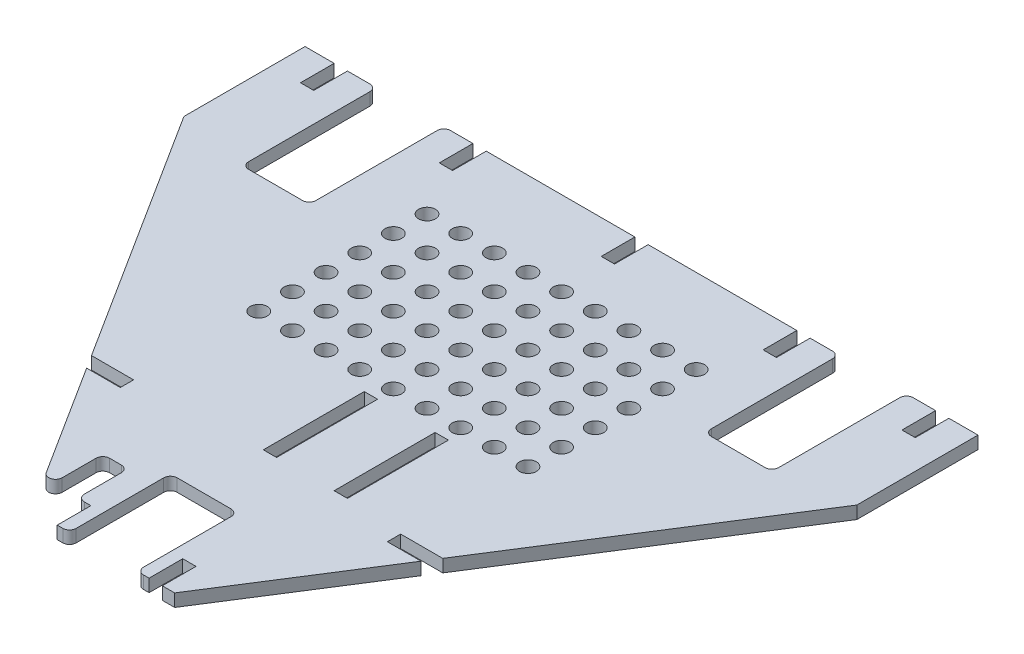
SolidWorks part; units mm, degrees
material "Corrugated Paper"
ref_plane "Front Plane" through (0, 0, 0) normal (0, 0, 1) x (1, 0, 0)
ref_plane "Top Plane" through (0, 0, 0) normal (0, 1, 0) x (1, 0, 0)
ref_plane "Right Plane" through (0, 0, 0) normal (1, 0, 0) x (0, 0, -1)
sketch "Sketch1" plane through (0, 0, 0) normal (0, 1, 0) x (1, 0, 0)
  line L0 (0, 0) -> (0, -142.875) construction
  line L1 (12.7, -63.5) -> (-12.7, -63.5)
  line L2 (-12.7, -63.5) -> (-12.7, -101.6)
  line L3 (-12.7, -101.6) -> (-17.3355, -101.6)
  line L4 (-26.9875, -101.6) -> (-127, 55.88)
  line L5 (-127, 55.88) -> (-127, 101.6)
  line L6 (-127, 101.6) -> (-116.0145, 101.6)
  line L7 (-100.0125, 101.6) -> (-100.0125, 50.8)
  line L9 (-100.0125, 50.8) -> (-74.6125, 50.8)
  line L10 (-74.6125, 50.8) -> (-74.6125, 101.6)
  line L11 (-74.6125, 101.6) -> (-63.627, 101.6)
  line L13 (74.6125, 50.8) -> (74.6125, 101.6)
  line L14 (100.0125, 50.8) -> (74.6125, 50.8)
  line L15 (100.0125, 101.6) -> (100.0125, 50.8)
  line L16 (127, 101.6) -> (116.0145, 101.6)
  line L17 (127, 55.88) -> (127, 101.6)
  line L18 (26.9875, -101.6) -> (127, 55.88)
  line L19 (12.7, -101.6) -> (17.3355, -101.6)
  line L20 (12.7, -63.5) -> (12.7, -101.6)
  line L21 (-127, 101.6) -> (127, -101.6) construction
  line L22 (-22.352, -101.6) -> (-26.9875, -101.6)
  line L24 (-22.352, -101.6) -> (-22.352, -88.9)
  line L25 (-22.352, -88.9) -> (-17.3355, -88.9)
  line L26 (-17.3355, -101.6) -> (-17.3355, -88.9)
  line L27 (22.352, -101.6) -> (22.352, -88.9)
  line L28 (22.352, -88.9) -> (17.3355, -88.9)
  line L29 (17.3355, -101.6) -> (17.3355, -88.9)
  line L30 (22.352, -101.6) -> (26.9875, -101.6)
  line L31 (-87.3125, 50.8) -> (-87.3125, 101.6) construction
  line L32 (-110.998, 101.6) -> (-100.0125, 101.6)
  line L34 (-116.0145, 101.6) -> (-116.0145, 88.9)
  line L35 (-116.0145, 88.9) -> (-110.998, 88.9)
  line L36 (-110.998, 101.6) -> (-110.998, 88.9)
  line L37 (-58.6105, 101.6) -> (-58.6105, 88.9)
  line L38 (-58.6105, 88.9) -> (-63.627, 88.9)
  line L39 (-63.627, 101.6) -> (-63.627, 88.9)
  line L40 (-58.6105, 101.6) -> (58.6105, 101.6)
  line L41 (116.0145, 101.6) -> (116.0145, 88.9)
  line L42 (116.0145, 88.9) -> (110.998, 88.9)
  line L43 (110.998, 101.6) -> (110.998, 88.9)
  line L44 (58.6105, 101.6) -> (58.6105, 88.9)
  line L45 (63.627, 101.6) -> (63.627, 88.9)
  line L46 (58.6105, 88.9) -> (63.627, 88.9)
  line L47 (63.627, 101.6) -> (74.6125, 101.6)
  line L48 (110.998, 101.6) -> (100.0125, 101.6)
  point P26 (0, -63.5)
  dimension "D2" = 25.4
  dimension "D3" = 254
  dimension "D5" = 38.1
  dimension "D6" = 50.8
  dimension "D7" = 203.2
  dimension "D8" = 45.72
  dimension "D9" = 26.9875
  dimension "D4" = 14.2875
  dimension "D10" = 5.0165
  dimension "D11" = 12.7
  dimension "D12" = 5.0165
extrude "Boss-Extrude1" add sketch "Sketch1" along normal blind 4.7625 contours L13 L47 L45 L46 L44 L40 L37 L38 L39 L11 L10 L9 L7 L32 L36 L35 L34 L6 L5 L4 L22 L24 L25 L26 L3 L2 L1 L20 L19 L29 L28 L27 L30 L18 L17 L16 L41 L42 L43 L48 L15 L14
sketch "Sketch2" plane through (0, 4.7625, 0) normal (0, 1, 0) x (1, 0, 0)
  line L0 (12.827, 0) -> (12.827, 54.8341) construction
  line L5 (-7.8105, -1021.0759) -> (-7.8105, 48978.9241) construction
  line L6 (-58.6105, 88.9) -> (-63.627, 88.9) construction
  line L7 (-3.048, 0) -> (1.9685, 0)
  line L8 (-3.048, 0) -> (-3.048, -38.1)
  line L9 (-3.048, -38.1) -> (1.9685, -38.1)
  line L10 (1.9685, 0) -> (1.9685, -38.1)
  line L11 (-22.352, -101.6) -> (-31.877, -101.6)
  line L12 (23.6855, 0) -> (23.6855, -38.1)
  line L13 (28.702, -38.1) -> (23.6855, -38.1)
  line L14 (28.702, 0) -> (28.702, -38.1)
  line L15 (28.702, 0) -> (23.6855, 0)
  line L16 (-22.352, -101.6) -> (-22.352, -69.85)
  line L17 (12.7, -63.5) -> (-12.7, -63.5) construction
  line L18 (-22.352, -69.85) -> (-31.877, -69.85)
  line L19 (-31.877, -101.6) -> (-31.877, -69.85)
  line L20 (-17.3355, -101.6) -> (-17.3355, -88.9) construction
  dimension "D2" = 25.4
  dimension "D3" = 31.75
  dimension "D1" = 38.1
  dimension "D5" = 9.525
  dimension "D6" = 31.75
  dimension "D7" = 9.525
  dimension "D4" = 9.525
extrude "Cut-Extrude1" cut sketch "Sketch2" against normal through all
fillet "Fillet1" radius 2.54 4 edges at (-22.352, 2.3813, 88.9) (-31.877, 2.3813, 93.901) (-22.352, 2.3813, 69.85) (-31.877, 2.3813, 69.85)
fillet "Fillet2" radius 2.54 12 edges at (-12.7, 2.3813, 101.6) (12.7, 2.3813, 101.6) (12.7, 2.3813, 63.5) (-12.7, 2.3813, 63.5) (100.0125, 2.3813, -101.6) (100.0125, 2.3813, -50.8) (74.6125, 2.3813, -101.6) (74.6125, 2.3813, -50.8) (-100.0125, 2.3813, -101.6) (-74.6125, 2.3813, -101.6) (-74.6125, 2.3813, -50.8) (-100.0125, 2.3813, -50.8)
sketch "Sketch3" plane through (0, 4.7625, 0) normal (0, 1, 0) x (1, 0, 0)
  line L0 (-74.6125, 53.34) -> (-74.6125, 99.06) construction
  line L1 (-58.6105, 88.9) -> (-63.627, 88.9) construction
  circle A0 centre (-49.2125, 69.85) radius 3.175
  dimension "D1" = 6.35
  dimension "D2" = 25.4
  dimension "D3" = 19.05
extrude "Cut-Extrude2" cut sketch "Sketch3" against normal through all
pattern_linear "LPattern1" count 9 spacing 12.7 along (1, 0, 0) count 6 spacing 12.7 along (0, 0, 1) of "Cut-Extrude2"
sketch "Sketch4" plane through (0, 4.7625, 0) normal (0, 1, 0) x (1, 0, 0)
  line L0 (0, -164.31) -> (0, 101.6) construction
  line L1 (-63.105, 101.6) -> (63.105, 101.6) construction
  line L2 (-63.105, 101.6) -> (-63.105, -164.31) construction
  line L3 (-63.105, -164.31) -> (63.105, -164.31) construction
  line L4 (63.105, 101.6) -> (63.105, -164.31) construction
  line L5 (26.9875, -101.6) -> (127, 55.88) construction
  line L6 (66.2909, -39.7128) -> (50.405, -39.7128)
  line L7 (66.2909, -39.7128) -> (66.2909, -44.7293)
  line L8 (66.2909, -44.7293) -> (50.405, -44.7293)
  line L9 (50.405, -39.7128) -> (50.405, -44.7293)
  line L10 (-50.405, -39.7128) -> (-50.405, -44.7293)
  line L11 (-66.2909, -44.7293) -> (-50.405, -44.7293)
  line L12 (-66.2909, -39.7128) -> (-66.2909, -44.7293)
  line L13 (-66.2909, -39.7128) -> (-50.405, -39.7128)
  line L14 (-58.6105, 101.6) -> (58.6105, 101.6) construction
  line L15 (-2.5082, 101.6) -> (2.5082, 101.6)
  line L16 (-2.5082, 101.6) -> (-2.5083, 88.9)
  line L17 (-2.5083, 88.9) -> (2.5083, 88.9)
  line L18 (2.5082, 101.6) -> (2.5083, 88.9)
  point P8 (63.105, -44.7293)
  point P11 (0, 101.6)
  point P24 (0, 0)
  point P26 (0, 0)
  point P27 (0, 0)
  point P28 (0, 0)
  point P29 (0, 0)
  point P30 (0, 0)
  point P31 (0, 0)
  point P32 (0, 0)
  point P33 (0, 0)
  point P34 (0, 0)
  point P35 (67.5169, -37.7823)
  point P36 (0, 0)
  point P37 (0, 0)
  point P38 (0, 0)
  point P39 (0, 0)
  point P40 (0, 0)
  point P41 (0, 0)
  point P42 (64.7518, -42.1362)
  dimension "D1" = 265.91
  dimension "D2" = 126.21
  dimension "D5" = 5.0165
  dimension "D6" = 12.7
  dimension "D4" = 12.7
  dimension "D3" = 5.0165
extrude "Cut-Extrude3" cut sketch "Sketch4" against normal through all
equation "\"D1@Boss-Extrude1\" = \"thick\""
equation "\"D4@Sketch1\" = \"thick\" * 3"
equation "\"D10@Sketch1\"=\"thick\"+\"clear\""
equation "\"D9@Sketch1\" = \"thick\" * 3 + 0.5"
equation "\"D12@Sketch1\"=\"thick\"+\"clear\""
equation "\"D3@Sketch2\"=\"MotorLength@Motor-1.Part\""
equation "\"D1@Sketch2\" =  ( \"MotorDiameter@Motor-1.Part\" + 0.5 ) "
equation "\"rodThick\"= 3/16in"
equation "\"thick\"= 3/16in"
equation "\"D5@Sketch2\"=2*\"thick\""
equation "\"clear\"= 0.01in"
equation "\"D7@Sketch2\"=2*\"thick\""
equation "\"D4@Sketch2\"=2*\"thick\""
equation "\"D5@Sketch4\"=\"thick\"+\"clear\""
